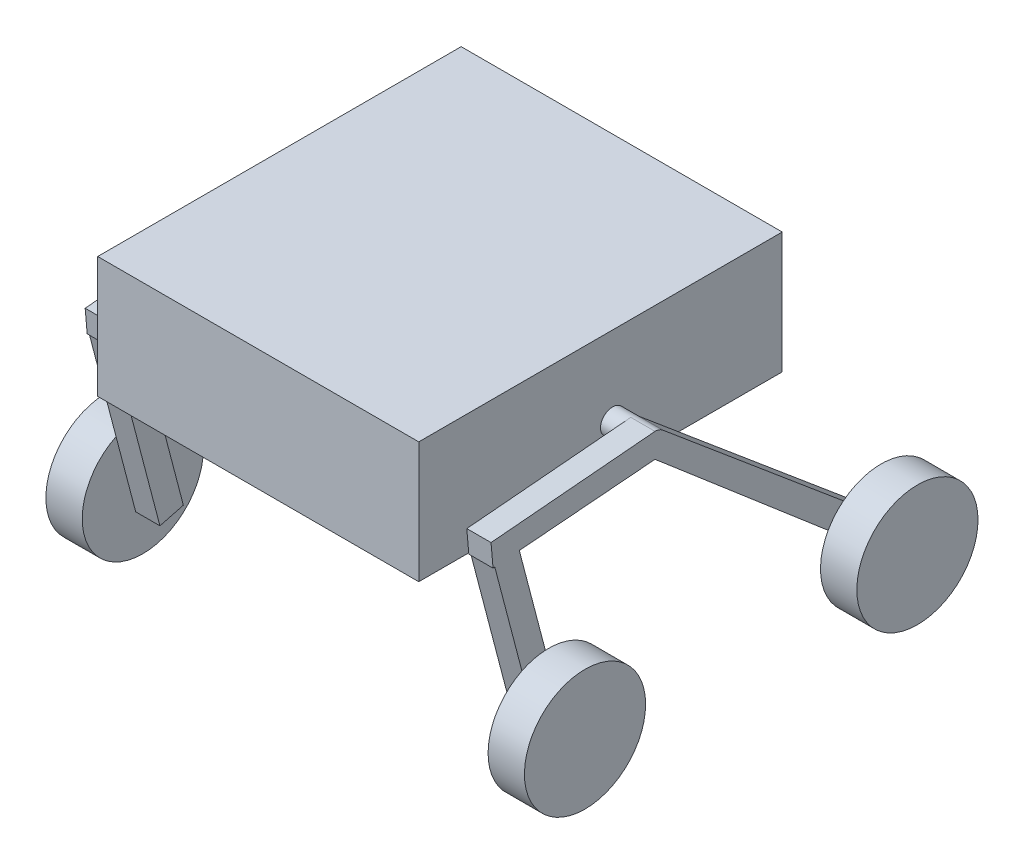
SolidWorks part; units mm, degrees
ref_plane "Front Plane" through (0, 0, 0) normal (0, 0, 1) x (1, 0, 0)
ref_plane "Top Plane" through (0, 0, 0) normal (0, 1, 0) x (1, 0, 0)
ref_plane "Right Plane" through (0, 0, 0) normal (1, 0, 0) x (0, 0, -1)
sketch "Sketch1" plane through (0, 0, 0) normal (0, 1, 0) x (1, 0, 0)
  line L0 (0, 0) -> (0, 762)
  line L1 (0, 762) -> (673.1, 762)
  line L2 (673.1, 762) -> (673.1, 0)
  line L3 (673.1, 0) -> (0, 0)
extrude "Boss-Extrude1" add sketch "Sketch1" along normal blind 254
sketch "Sketch2" plane through (673.1, 0, 0) normal (1, 0, 0) x (0, 0, -1)
  line L0 (762, 88.9) -> (406.4, 88.9) construction
  line L2 (0, 0) -> (762, 0) construction
  line L3 (762, 254) -> (762, 0) construction
  circle A0 centre (406.4, 88.9) radius 25.4
  dimension "D2" = 355.6
  dimension "D1" = 88.9
extrude "Boss-Extrude2" add sketch "Sketch2" along normal blind 38.1
sketch "Sketch3" plane through (711.2, 0, 0) normal (1, 0, 0) x (0, 0, -1)
  line L9 (406.4, 88.9) -> (909.5288, -333.2752) construction
  line L11 (422.7268, 108.3575) -> (925.8556, -313.8177)
  line L12 (925.8556, -313.8177) -> (909.5288, -333.2752)
  line L13 (909.5288, -333.2752) -> (893.202, -352.7327)
  line L14 (893.202, -352.7327) -> (406.4, 63.5)
  line L16 (406.4, 88.9) -> (0, 88.9) construction
  line L17 (0, 254) -> (0, 0) construction
  line L18 (406.4, 88.9) -> (25.4342, 55.5698) construction
  line L19 (406.4, 88.9) -> (90.1082, 61.2281) construction
  line L20 (64.8048, 59.0143) -> (66.8457, 35.6871)
  line L21 (64.8048, 59.0143) -> (62.5911, 84.3176)
  line L22 (62.5911, 84.3176) -> (406.4, 114.3)
  line L23 (66.8457, 35.6871) -> (70.4653, 35.9836)
  line L26 (90.1082, 61.2281) -> (193.1163, -331.9008) construction
  line L27 (193.1163, -331.9008) -> (217.6868, -325.4628)
  line L28 (193.1163, -331.9008) -> (168.5457, -338.3388)
  line L29 (168.5457, -338.3388) -> (70.4653, 35.9836)
  line L30 (217.6868, -325.4628) -> (121.8768, 40.1947)
  line L31 (121.8768, 40.1947) -> (406.4, 63.5)
  circle A0 centre (406.4, 88.9) radius 25.4 construction
  circle A1 centre (406.4, 88.9) radius 25.4 construction
  arc A2 (406.4, 114.3) -> (422.7268, 108.3575) centre (406.4, 88.9) cw
  dimension "D1" = 80
  dimension "D2" = 135
  dimension "D3" = 5
extrude "Boss-Extrude3" add sketch "Sketch3" along normal blind 50.8
sketch "Sketch4" plane through (762, 0, 0) normal (1, 0, 0) x (0, 0, -1)
  line L0 (193.1163, -331.9008) -> (183.4593, -295.045) construction
  line L1 (168.5457, -338.3388) -> (217.6868, -325.4628) construction
  line L2 (909.5288, -333.2752) -> (880.3425, -308.785) construction
  line L3 (893.202, -352.7327) -> (925.8556, -313.8177) construction
  circle A2 centre (183.4593, -295.045) radius 127
  circle A3 centre (880.3425, -308.785) radius 127
extrude "Boss-Extrude4" add sketch "Sketch4" along normal blind 76.2
ref_plane "Plane1" through (336.55, 0, 0) normal (1, 0, 0) x (0, 0, -1)
mirror "Mirror1" about plane through (336.55, 0, 0) normal (1, 0, 0) of "Boss-Extrude4", "Boss-Extrude3", "Boss-Extrude2"
ref_axis "Axis1" through (762, 88.9, -406.4) along (-1, 0, 0)
